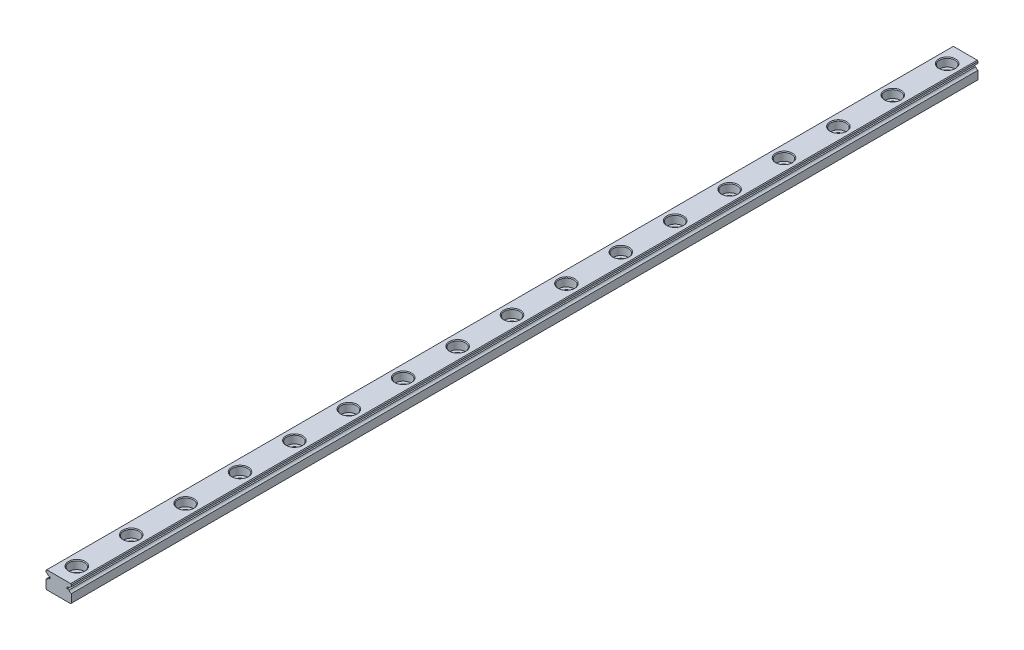
SolidWorks part; units mm, degrees
ref_plane "Спереди" through (0, 0, 0) normal (0, 0, 1) x (1, 0, 0)
ref_plane "Сверху" through (0, 0, 0) normal (0, 1, 0) x (1, 0, 0)
ref_plane "Справа" through (0, 0, 0) normal (1, 0, 0) x (0, 0, -1)
sketch "Sketch1" plane through (0, 0, 0) normal (0, 0, 1) x (1, 0, 0)
  line L0 (0, 0) -> (0, 4.3706) construction
  line L1 (-3.3, -2.4) -> (3.3, -2.4)
  line L2 (-3.5, -2.2) -> (-3.5, 0.1063)
  line L3 (-3.3, 2.4) -> (3.3, 2.4)
  line L4 (3.5, -2.2) -> (3.5, 0.1063)
  line L5 (-3.5, -2.4) -> (3.5, 2.4) construction
  line L6 (-3.5, 2.4) -> (3.5, -2.4) construction
  line L7 (-3.5, 1.6937) -> (-3.5, 2.2)
  line L8 (3.5, 1.6937) -> (3.5, 2.2)
  line L9 (-3.5, -2.2) -> (-3.3, -2.4)
  line L10 (3.3, -2.4) -> (3.5, -2.2)
  line L11 (3.3, 2.4) -> (3.5, 2.2)
  line L12 (-3.5, 2.2) -> (-3.3, 2.4)
  line L13 (2.8401, 0.65) -> (2.3401, 0.65)
  line L14 (-2.8401, 0.65) -> (-2.3401, 0.65)
  line L15 (2.3401, 0.65) -> (2.3401, 1.15)
  line L16 (-2.8401, 1.15) -> (-2.3401, 1.15)
  line L17 (-2.3401, 0.65) -> (-2.3401, 1.15)
  line L18 (2.8401, 1.15) -> (2.3401, 1.15)
  arc A0 (-3.5, 1.6937) -> (-2.8401, 1.15) centre (-3.6, 0.9) cw
  arc A1 (3.5, 1.6937) -> (2.8401, 1.15) centre (3.6, 0.9) ccw
  arc A2 (-2.8401, 0.65) -> (-3.5, 0.1063) centre (-3.6, 0.9) cw
  arc A3 (2.8401, 0.65) -> (3.5, 0.1063) centre (3.6, 0.9) ccw
  point P0 (0, 0)
  dimension "D4" = 0.8
  dimension "D5" = 0.1
  dimension "D1" = 7
  dimension "D2" = 4.8
  dimension "D3" = 1.5
  dimension "D6" = 0.5
  dimension "D7" = 0.5
extrude "Extrude1" add sketch "Sketch1" along normal blind 250
sketch "Sketch2" plane through (0, 2.4, 0) normal (0, 1, 0) x (1, 0, 0)
  line L0 (0, 0) -> (0, -5) construction
  circle A0 centre (0, -5) radius 1.2
  circle A1 centre (0, -5) radius 2.1
  dimension "D1" = 2.4
  dimension "D2" = 4.2
  dimension "D3" = 5
extrude "Extrude2" cut sketch "Sketch2" against normal up to next contours A0 region at (0, 2.4, 5)
extrude "Extrude4" cut sketch "Sketch" against normal blind 2.3
sketch "Sketch" plane through (0, 2.4, 0) normal (0, 1, 0) x (1, 0, 0) same geometry as "Sketch2"
chamfer "Chamfer1" distance 0.2 angle 45 2 edges at (0, -2.4, 6.2) (0, 2.4, 7.1)
pattern_linear "LPattern1" count 17 spacing 15 along (0, 0, 1) of "Extrude4", "Chamfer1", "Extrude2"
